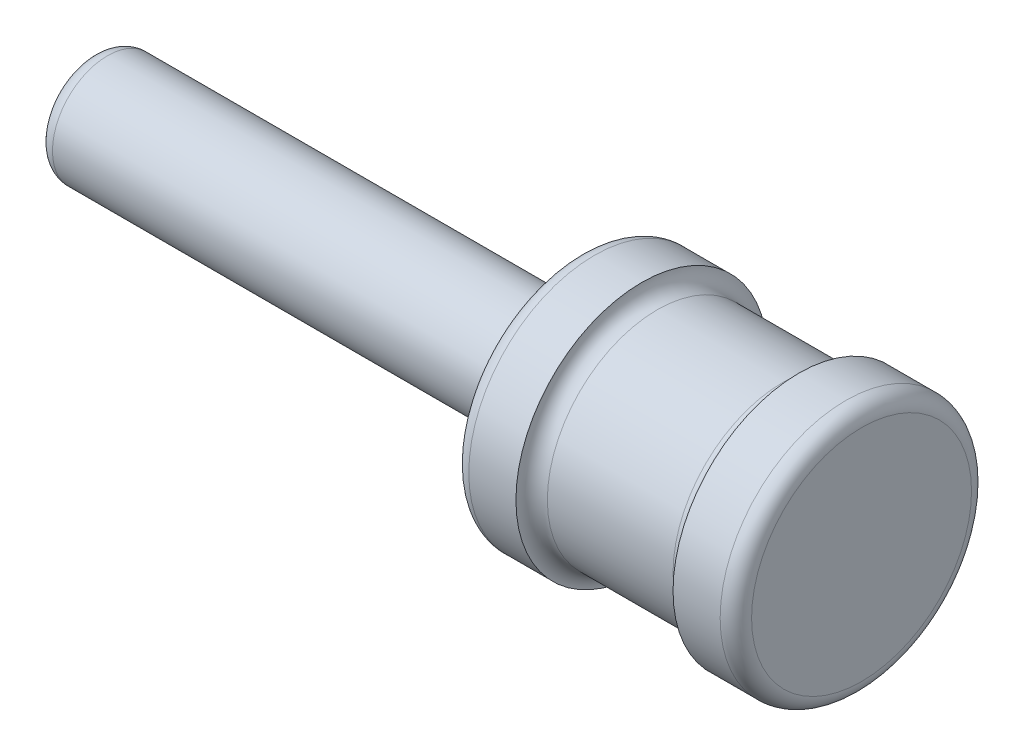
SolidWorks part; units mm, degrees
ref_plane "Ebene vorne" through (0, 0, 0) normal (0, 0, 1) x (1, 0, 0)
ref_plane "Ebene oben" through (0, 0, 0) normal (0, 1, 0) x (1, 0, 0)
ref_plane "Ebene rechts" through (0, 0, 0) normal (1, 0, 0) x (0, 0, -1)
sketch "Skizze1" plane through (0, 0, 0) normal (0, 0, 1) x (1, 0, 0)
  line L0 (0, 0) -> (-24.5, 0)
  line L1 (-24.5, 0) -> (-24.5, 1.75)
  line L2 (-24.5, 1.75) -> (-9, 1.75)
  line L3 (-9, 1.75) -> (-9, 4)
  line L4 (-9, 4) -> (-7, 4)
  line L5 (-7, 4) -> (-7, 3.5)
  line L6 (-7, 3.5) -> (-2, 3.5)
  line L7 (-2, 3.5) -> (-2, 4)
  line L8 (-2, 4) -> (0, 4)
  line L9 (0, 4) -> (0, 0)
  dimension "D1" = 1.75
  dimension "D2" = 4
  dimension "D3" = 3.5
  dimension "D4" = 4
  dimension "D5" = 5
  dimension "D6" = 2
  dimension "D7" = 2
  dimension "D8" = 15.5
revolve "Rotation1" add sketch "Skizze1" angle 360 about L0
fillet "Verrundung1" radius 0.5 5 edges at (-24.5, 1.75, 0) (0, 4, 0) (-9, 4, 0) (-2, 3.5, 0) (-7, 3.5, 0)
